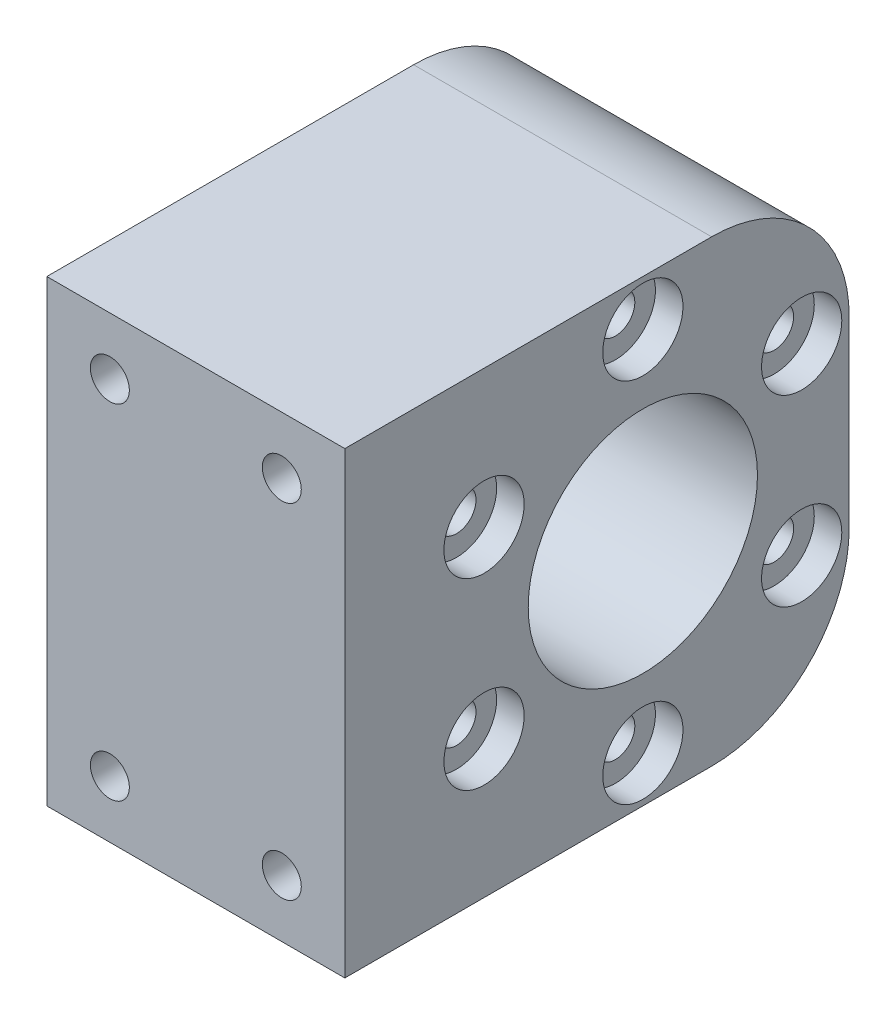
SolidWorks part; units mm, degrees
material "7075-O (SS)"
ref_plane "Front" through (0, 0, 0) normal (0, 0, 1) x (1, 0, 0)
ref_plane "Top" through (0, 0, 0) normal (0, 1, 0) x (1, 0, 0)
ref_plane "Right" through (0, 0, 0) normal (1, 0, 0) x (0, 0, -1)
sketch "Croquis1" plane through (0, 0, 0) normal (0, 0, 1) x (1, 0, 0)
  line L1 (-13, -20) -> (13, -20)
  line L2 (-13, -20) -> (-13, 20)
  line L3 (-13, 20) -> (13, 20)
  line L4 (13, -20) -> (13, 20)
  line L5 (-13, -20) -> (13, 20) construction
  line L6 (-13, 20) -> (13, -20) construction
  point P0 (0, 0)
  dimension "D1" = 40
  dimension "D2" = 26
extrude "Saliente-Extruir1" add sketch "Croquis1" along normal mid plane 52
hole_wizard "Taladro de margen para M31" positions "Croquis2" profile "Croquis3" hole size "M3" standard "Ansi Metric"
sketch "Croquis2" plane through (0, 0, 26) normal (0, 0, 1) x (1, 0, 0)
  line L1 (7.5, -15) -> (-7.5, -15) construction
  line L2 (7.5, -15) -> (7.5, 15) construction
  line L3 (7.5, 15) -> (-7.5, 15) construction
  line L4 (-7.5, -15) -> (-7.5, 15) construction
  line L5 (7.5, -15) -> (-7.5, 15) construction
  line L6 (7.5, 15) -> (-7.5, -15) construction
  point P2 (-7.5, 15)
  point P47 (7.5, -15)
  point P48 (7.5, 15)
  point P49 (-7.5, -15)
  dimension "D1" = 30
  dimension "D2" = 15
sketch "Croquis3" plane through (-7.5, 15, 26) normal (1, 0, 0) x (0, -1, 0)
  line L0 (0, 0) -> (0, 16.0215)
  line L1 (0, 16.0215) -> (1.7, 15)
  line L2 (1.7, 15) -> (1.7, 0)
  line L5 (1.7, 0) -> (0, 0)
  line L10 (0, 16.0215) -> (-1.7, 15) construction
  line L11 (0, -6.35) -> (0, 107.95) construction
  dimension "Diámetro de taladro" = 3.4
  dimension "Profundidad de taladro" = 15
  dimension "Ángulo de perforador" = 118
hole_wizard "Refrentado para tornillo con cabeza troncocónica de M31" positions "Croquis4" profile "Croquis6" counterbore size "M3" standard "Ansi Metric" end condition through all
sketch "Croquis4" plane through (13, 0, 0) normal (1, 0, 0) x (0, 0, -1)
  line L0 (0, 14.3) -> (0, -14.3) construction
  point P1 (0, 16)
  point P11 (13.8564, 8)
  point P12 (13.8564, -8)
  point P13 (0, -16)
  point P14 (-13.8564, -8)
  point P15 (-13.8564, 8)
  dimension "D1" = 16
  dimension "D2" = 6
sketch "Croquis6" plane through (13, 16, 0) normal (0, 1, 0) x (0, 0, -1)
  line L0 (0, 0) -> (0, 26)
  line L1 (0, 26) -> (1.7, 26)
  line L3 (1.7, 26) -> (1.7, 2.4)
  line L4 (1.7, 2.4) -> (3.5, 2.4)
  line L5 (3.5, 2.4) -> (3.5, 0)
  line L7 (3.5, 0) -> (0, 0)
  line L11 (0, -6.35) -> (0, 107.95) construction
  dimension "Diámetro de taladro hasta el siguiente" = 3.4
  dimension "Profundidad de taladro hasta el siguiente" = 26
  dimension "Diámetro de refrentado" = 7
  dimension "Profundidad de refrentado" = 2.4
sketch "Croquis7" plane through (-13, 0, 0) normal (-1, 0, 0) x (0, 0, 1)
  circle A0 centre (0, 0) radius 10
  dimension "D1" = 20
extrude "Cortar-Extruir1" cut sketch "Croquis7" against normal through all
sketch "Croquis9" plane through (13, 0, 0) normal (1, 0, 0) x (0, 0, -1)
  line L0 (-26, -20) -> (26, -20) construction
  line L1 (26, 20) -> (18, 20)
  line L2 (26, 20) -> (26, -20)
  line L3 (26, -20) -> (18, -20)
  line L4 (18, 20) -> (18, -20)
  dimension "D1" = 8
extrude "Cortar-Extruir3" cut sketch "Croquis9" against normal through all
fillet "Redondeo3" radius 12 2 edges at (0, -20, -18) (0, 20, -18)
